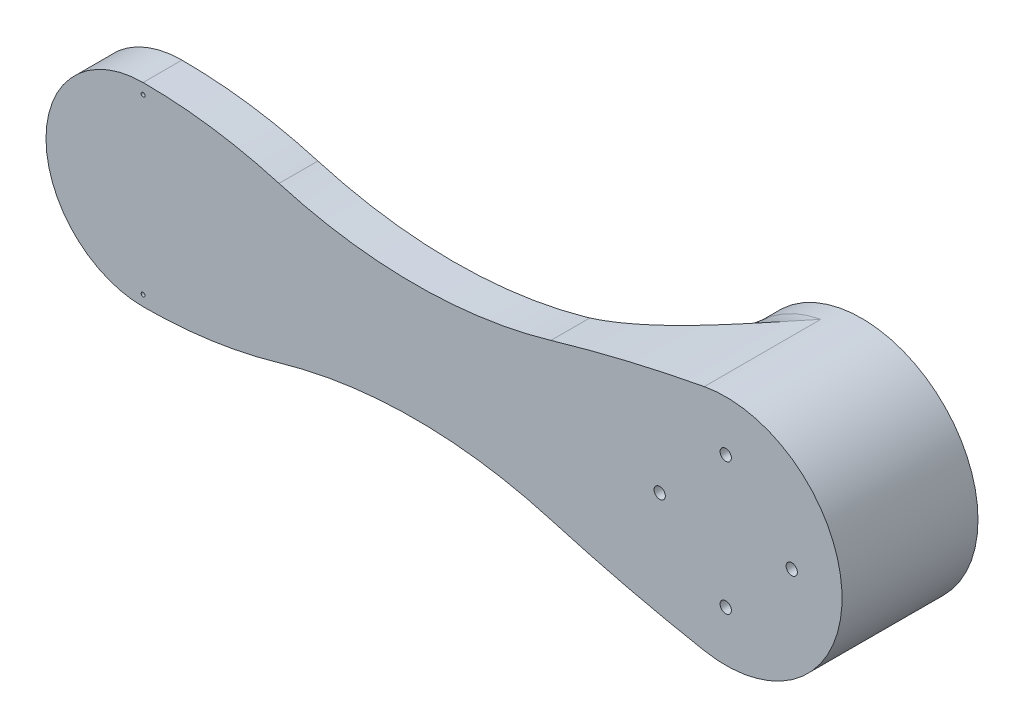
SolidWorks part; units mm, degrees
ref_plane "Front Plane" through (0, 0, 0) normal (0, 0, 1) x (1, 0, 0)
ref_plane "Top Plane" through (0, 0, 0) normal (0, 1, 0) x (1, 0, 0)
ref_plane "Right Plane" through (0, 0, 0) normal (1, 0, 0) x (0, 0, -1)
sketch "Sketch1" plane through (0, 0, 0) normal (0, 0, 1) x (1, 0, 0)
  circle A0 centre (0, 0) radius 24.95
  circle A1 centre (0, 0) radius 29.95
  circle A2 centre (0, 0) radius 24.75 construction
  dimension "D1" = 0.2
  dimension "D2" = 5
extrude "Boss-Extrude1" add sketch "Sketch1" along normal blind 30
sketch "Sketch2" plane through (0, 0, 30) normal (0, 0, 1) x (1, 0, 0)
  circle A0 centre (0, 0) radius 29.95 construction
  circle A1 centre (0, 0) radius 29.95
extrude "Boss-Extrude2" add sketch "Sketch2" along normal blind 5
sketch "Sketch3" plane through (0, 0, 30) normal (0, 0, -1) x (-1, 0, 0)
  circle A0 centre (0, 17) radius 3.35
  circle A1 centre (-17, 0) radius 3.35
  circle A2 centre (0, -17) radius 3.35
  circle A3 centre (17, 0) radius 3.35
  circle A4 centre (0, 17) radius 3.5 construction
  dimension "D1" = 0.15
extrude "Boss-Extrude3" add sketch "Sketch3" along normal blind 5
sketch "Sketch4" plane through (0, 0, 25) normal (0, 0, -1) x (-1, 0, 0)
  circle A0 centre (0, 17) radius 1.45
  circle A1 centre (17, 0) radius 1.45
  circle A2 centre (-17, 0) radius 1.45
  circle A3 centre (0, -17) radius 1.45
  dimension "D1" = 2.9
extrude "Cut-Extrude1" cut sketch "Sketch4" against normal through all
fillet "Fillet1" radius 2 1 edges at (24.95, 0, 0)
fillet "Fillet2" radius 1 4 edges at (-3.35, -17, 25) (-20.35, 0, 25) (-3.35, 17, 25) (13.65, 0, 25)
sketch "Sketch5" plane through (0, 0, 35) normal (0, 0, 1) x (1, 0, 0)
  line L0 (-150, 0) -> (0, 0) construction
  line L1 (-115, -20) -> (-45, -20) construction
  line L2 (-80, -20) -> (-80, 0) construction
  line L3 (-150, 22.279) -> (-150, -22.279) construction
  arc A0 (-5.523, 29.4364) -> (-45, 20) centre (70.6322, -376.4534) ccw
  arc A1 (-150, 25) -> (-150, -25) centre (-150, 0) ccw
  arc A2 (-45, 20) -> (-115, 20) centre (-80, 140) cw
  arc A3 (-5.523, -29.4364) -> (-45, -20) centre (70.6322, 376.4534) cw
  circle A4 centre (0, 0) radius 29.95 construction
  arc A5 (-45, -20) -> (-115, -20) centre (-80, -140) ccw
  arc A6 (-115, -20) -> (-150, -25) centre (-150, 100) cw
  arc A7 (-115, 20) -> (-150, 25) centre (-150, -100) ccw
  arc A8 (-5.523, -29.4364) -> (-5.523, 29.4364) centre (0, 0) cw
  circle A9 centre (-150, -22.279) radius 0.5
  circle A10 centre (-150, 22.279) radius 0.5
  dimension "D2" = 25
  dimension "D6" = 1
  dimension "D1" = 150
  dimension "D3" = 15
  dimension "D4" = 70
  dimension "D5" = 80
extrude "Boss-Extrude4" add sketch "Sketch5" against normal blind 10
fillet "Fillet3" radius 20 1 edges at (-29.95, 0, 25)
